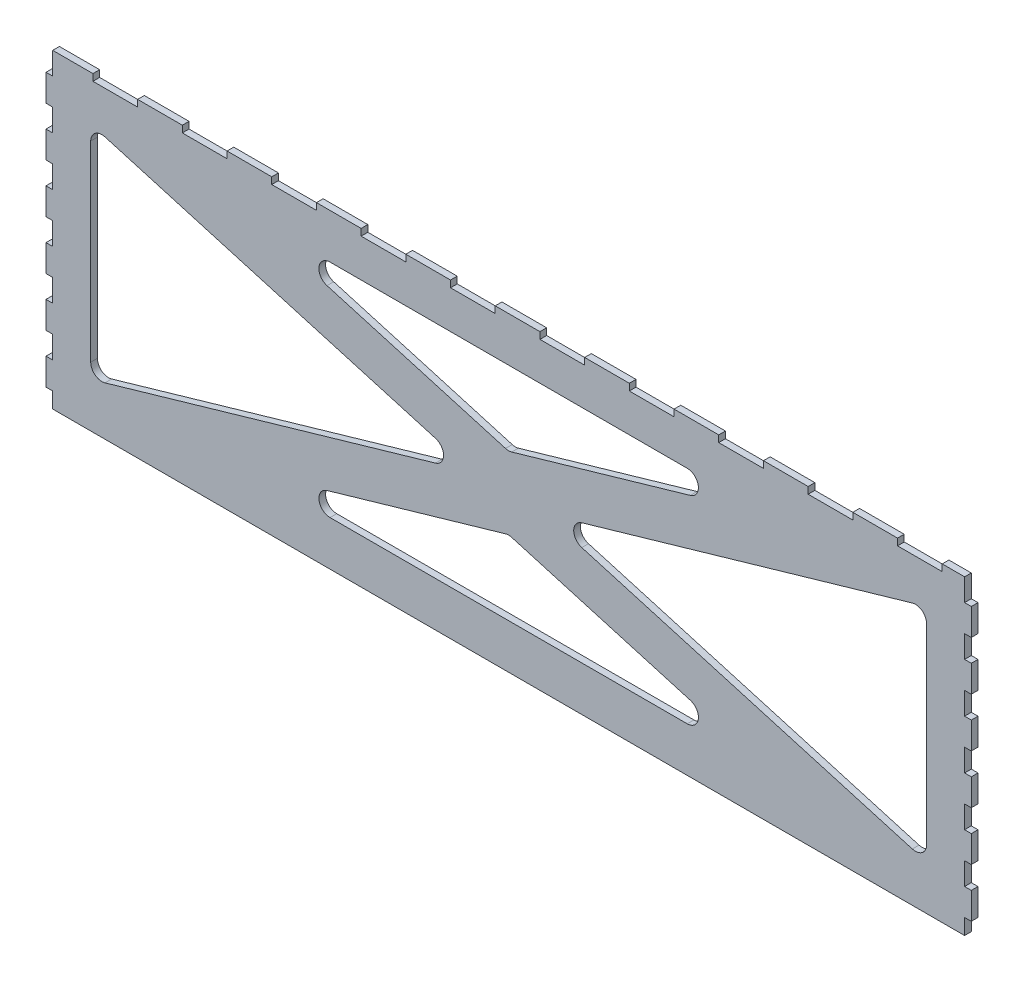
SolidWorks part; units mm, degrees
material "birch 3mm plywood"
ref_plane "Front Plane" through (0, 0, 0) normal (0, 0, 1) x (1, 0, 0)
ref_plane "Top Plane" through (0, 0, 0) normal (0, 1, 0) x (1, 0, 0)
ref_plane "Right Plane" through (0, 0, 0) normal (1, 0, 0) x (0, 0, -1)
sketch "Sketch1" plane through (0, 0, 152) normal (0, 0, 1) x (1, 0, 0)
  line L1 (-207, 69.5) -> (207, 69.5)
  line L2 (-207, 69.5) -> (-207, -69.5)
  line L3 (-207, -69.5) -> (207, -69.5)
  line L4 (207, 69.5) -> (207, -69.5)
  line L6 (-187, -42.8458) -> (-187, 42.8458)
  line L7 (-180.6086, 47.6483) -> (-32.7214, 4.8025)
  line L12 (200, -62.5) -> (-200, -62.5) construction
  line L13 (200, 62.5) -> (200, -62.5) construction
  line L14 (-200, -62.5) -> (-200, 62.5) construction
  line L15 (-200, 62.5) -> (200, 62.5) construction
  line L18 (79.903, 49.5) -> (-79.903, 49.5)
  line L19 (-32.7214, -4.8025) -> (-180.6086, -47.6483)
  line L20 (-81.2943, 39.6975) -> (-1.3914, 16.5481)
  line L21 (1.3914, 16.5481) -> (81.2943, 39.6975)
  line L23 (180.6086, 47.6483) -> (32.7214, 4.8025)
  line L24 (187, -42.8458) -> (187, 42.8458)
  line L25 (32.7214, -4.8025) -> (180.6086, -47.6483)
  line L26 (-200, 0) -> (200, 0) construction
  line L27 (-81.2943, -39.6975) -> (-1.3914, -16.5481)
  line L28 (79.903, -49.5) -> (-79.903, -49.5)
  line L29 (1.3914, -16.5481) -> (81.2943, -39.6975)
  line L30 (0, 16.145) -> (0, -16.145) construction
  line L31 (-16.145, 0) -> (16.145, 0) construction
  line L32 (0, 16.145) -> (0, -16.145) construction
  arc A0 (-180.6086, -47.6483) -> (-187, -42.8458) centre (-182, -42.8458) cw
  arc A1 (-32.7214, -4.8025) -> (-32.7214, 4.8025) centre (-34.1127, 0) ccw
  arc A2 (-180.6086, 47.6483) -> (-187, 42.8458) centre (-182, 42.8458) ccw
  arc A3 (81.2943, -39.6975) -> (79.903, -49.5) centre (79.903, -44.5) cw
  arc A4 (-81.2943, -39.6975) -> (-79.903, -49.5) centre (-79.903, -44.5) ccw
  arc A5 (-1.3914, -16.5481) -> (1.3914, -16.5481) centre (0, -21.3506) cw
  arc A6 (32.7214, 4.8025) -> (32.7214, -4.8025) centre (34.1127, 0) ccw
  arc A7 (180.6086, -47.6483) -> (187, -42.8458) centre (182, -42.8458) ccw
  arc A8 (187, 42.8458) -> (180.6086, 47.6483) centre (182, 42.8458) ccw
  arc A9 (-81.2943, 39.6975) -> (-79.903, 49.5) centre (-79.903, 44.5) cw
  arc A10 (81.2943, 39.6975) -> (79.903, 49.5) centre (79.903, 44.5) ccw
  arc A11 (1.3914, 16.5481) -> (-1.3914, 16.5481) centre (0, 21.3506) cw
  point P14 (0, 0)
  point P15 (0, 0)
  point P32 (-187, 49.5)
  point P35 (115.1288, -49.5)
  point P38 (-115.1288, -49.5)
  point P51 (-115.1288, 49.5)
  point P54 (115.1288, 49.5)
  dimension "D9" = 5
  dimension "D10" = 5
  dimension "D1" = 7
  dimension "D2" = 7
  dimension "D3" = 7
  dimension "D4" = 7
  dimension "D5" = 20
  dimension "D6" = 20
  dimension "D7" = 20
  dimension "D8" = 20
  dimension "D11" = 20
  dimension "D12" = 400
  dimension "D13" = 125
extrude "Boss-Extrude1" add sketch "Sketch1" along normal blind 3
sketch "Sketch2" plane through (-207, 0, 0) normal (-1, 0, 0) x (0, 0, 1)
  line L76 (152, -18.5) -> (152, -28.5)
  line L77 (152, -28.5) -> (155, -28.5)
  line L78 (155, -28.5) -> (155, -40.5)
  line L79 (155, -40.5) -> (152, -40.5)
  line L80 (152, -40.5) -> (152, -50.5)
  line L81 (152, -50.5) -> (155, -50.5)
  line L82 (155, -50.5) -> (155, -62.5)
  line L83 (155, -62.5) -> (152, -62.5)
  line L84 (152, -62.5) -> (152, -69.5)
  line L85 (152, -69.5) -> (316, -69.5)
  line L86 (316, -69.5) -> (316, -62.5)
  line L87 (316, -62.5) -> (313, -62.5)
  line L88 (313, -62.5) -> (313, -50.5)
  line L89 (313, -50.5) -> (316, -50.5)
  line L90 (316, -50.5) -> (316, -40.5)
  line L91 (316, -40.5) -> (313, -40.5)
  line L92 (313, -40.5) -> (313, -28.5)
  line L93 (313, -28.5) -> (316, -28.5)
  line L94 (316, -28.5) -> (316, -18.5)
  line L95 (316, -18.5) -> (313, -18.5)
  line L96 (313, -18.5) -> (313, -6.5)
  line L97 (313, -6.5) -> (316, -6.5)
  line L98 (316, -6.5) -> (316, 3.5)
  line L99 (316, 3.5) -> (313, 3.5)
  line L100 (313, 3.5) -> (313, 15.5)
  line L101 (313, 15.5) -> (316, 15.5)
  line L102 (316, 15.5) -> (316, 25.5)
  line L103 (316, 47.5) -> (313, 47.5)
  line L104 (313, 47.5) -> (313, 59.5)
  line L105 (313, 59.5) -> (316, 59.5)
  line L106 (316, 59.5) -> (316, 69.5)
  line L107 (316, 69.5) -> (305, 69.5)
  line L108 (305, 69.5) -> (305, 66.5)
  line L109 (305, 66.5) -> (295, 66.5)
  line L110 (295, 66.5) -> (295, 69.5)
  line L111 (295, 69.5) -> (283, 69.5)
  line L112 (283, 69.5) -> (283, 66.5)
  line L113 (283, 66.5) -> (273, 66.5)
  line L114 (273, 66.5) -> (273, 69.5)
  line L115 (273, 69.5) -> (261, 69.5)
  line L116 (261, 69.5) -> (261, 66.5)
  line L117 (261, 66.5) -> (251, 66.5)
  line L118 (251, 66.5) -> (251, 69.5)
  line L119 (251, 69.5) -> (239, 69.5)
  line L120 (239, 69.5) -> (239, 66.5)
  line L121 (239, 66.5) -> (229, 66.5)
  line L122 (229, 66.5) -> (229, 69.5)
  line L123 (229, 69.5) -> (217, 69.5)
  line L124 (217, 69.5) -> (217, 66.5)
  line L125 (217, 66.5) -> (207, 66.5)
  line L126 (207, 66.5) -> (207, 69.5)
  line L127 (207, 69.5) -> (195, 69.5)
  line L128 (195, 69.5) -> (195, 66.5)
  line L129 (195, 66.5) -> (185, 66.5)
  line L130 (185, 66.5) -> (185, 69.5)
  line L131 (185, 69.5) -> (173, 69.5)
  line L132 (173, 69.5) -> (173, 66.5)
  line L133 (173, 66.5) -> (163, 66.5)
  line L134 (163, 66.5) -> (163, 69.5)
  line L135 (163, 69.5) -> (152, 69.5)
  line L136 (152, 69.5) -> (152, 59.5)
  line L137 (152, 59.5) -> (155, 59.5)
  line L138 (155, 59.5) -> (155, 47.5)
  line L139 (155, 47.5) -> (152, 47.5)
  line L140 (152, 47.5) -> (152, 37.5)
  line L141 (152, 37.5) -> (155, 37.5)
  line L142 (155, 37.5) -> (155, 25.5)
  line L143 (155, 25.5) -> (152, 25.5)
  line L144 (152, 25.5) -> (152, 15.5)
  line L145 (152, 15.5) -> (155, 15.5)
  line L146 (155, 15.5) -> (155, 3.5)
  line L147 (155, 3.5) -> (152, 3.5)
  line L148 (152, 3.5) -> (152, -6.5)
  line L149 (152, -6.5) -> (155, -6.5)
  line L150 (155, -6.5) -> (155, -18.5)
  line L151 (155, -18.5) -> (152, -18.5)
  line L152 (152, -18.5) -> (152, -28.5)
  line L153 (152, -28.5) -> (155, -28.5)
  line L154 (155, -28.5) -> (155, -40.5)
  line L155 (155, -40.5) -> (152, -40.5)
  line L156 (152, -40.5) -> (152, -50.5)
  line L157 (152, -50.5) -> (155, -50.5)
  line L158 (155, -50.5) -> (155, -62.5)
  line L159 (155, -62.5) -> (152, -62.5)
  line L160 (152, -62.5) -> (152, -69.5)
  line L161 (152, -69.5) -> (316, -69.5)
  line L162 (316, -69.5) -> (316, -62.5)
  line L163 (316, -62.5) -> (313, -62.5)
  line L164 (313, -62.5) -> (313, -50.5)
  line L165 (313, -50.5) -> (316, -50.5)
  line L166 (316, -50.5) -> (316, -40.5)
  line L167 (316, -40.5) -> (313, -40.5)
  line L168 (313, -40.5) -> (313, -28.5)
  line L169 (313, -28.5) -> (316, -28.5)
  line L170 (316, -28.5) -> (316, -18.5)
  line L171 (316, -18.5) -> (313, -18.5)
  line L172 (313, -18.5) -> (313, -6.5)
  line L173 (313, -6.5) -> (316, -6.5)
  line L174 (316, -6.5) -> (316, 3.5)
  line L175 (316, 3.5) -> (313, 3.5)
  line L176 (313, 3.5) -> (313, 15.5)
  line L177 (313, 15.5) -> (316, 15.5)
  line L178 (316, 15.5) -> (316, 25.5)
  line L179 (316, 47.5) -> (313, 47.5)
  line L180 (313, 47.5) -> (313, 59.5)
  line L181 (313, 59.5) -> (316, 59.5)
  line L182 (316, 59.5) -> (316, 69.5)
  line L183 (316, 69.5) -> (305, 69.5)
  line L184 (305, 69.5) -> (305, 66.5)
  line L185 (305, 66.5) -> (295, 66.5)
  line L186 (295, 66.5) -> (295, 69.5)
  line L187 (295, 69.5) -> (283, 69.5)
  line L188 (283, 69.5) -> (283, 66.5)
  line L189 (283, 66.5) -> (273, 66.5)
  line L190 (273, 66.5) -> (273, 69.5)
  line L191 (273, 69.5) -> (261, 69.5)
  line L192 (261, 69.5) -> (261, 66.5)
  line L193 (261, 66.5) -> (251, 66.5)
  line L194 (251, 66.5) -> (251, 69.5)
  line L195 (251, 69.5) -> (239, 69.5)
  line L196 (239, 69.5) -> (239, 66.5)
  line L197 (239, 66.5) -> (229, 66.5)
  line L198 (229, 66.5) -> (229, 69.5)
  line L199 (229, 69.5) -> (217, 69.5)
  line L200 (217, 69.5) -> (217, 66.5)
  line L201 (217, 66.5) -> (207, 66.5)
  line L202 (207, 66.5) -> (207, 69.5)
  line L203 (207, 69.5) -> (195, 69.5)
  line L204 (195, 69.5) -> (195, 66.5)
  line L205 (195, 66.5) -> (185, 66.5)
  line L206 (185, 66.5) -> (185, 69.5)
  line L207 (185, 69.5) -> (173, 69.5)
  line L208 (173, 69.5) -> (173, 66.5)
  line L209 (173, 66.5) -> (163, 66.5)
  line L210 (163, 66.5) -> (163, 69.5)
  line L211 (163, 69.5) -> (152, 69.5)
  line L212 (152, 69.5) -> (152, 59.5)
  line L213 (152, 59.5) -> (155, 59.5)
  line L214 (155, 59.5) -> (155, 47.5)
  line L215 (155, 47.5) -> (152, 47.5)
  line L216 (152, 47.5) -> (152, 37.5)
  line L217 (152, 37.5) -> (155, 37.5)
  line L218 (155, 37.5) -> (155, 25.5)
  line L219 (155, 25.5) -> (152, 25.5)
  line L220 (152, 25.5) -> (152, 15.5)
  line L221 (152, 15.5) -> (155, 15.5)
  line L222 (155, 15.5) -> (155, 3.5)
  line L223 (155, 3.5) -> (152, 3.5)
  line L224 (152, 3.5) -> (152, -6.5)
  line L225 (152, -6.5) -> (155, -6.5)
  line L226 (155, -6.5) -> (155, -18.5)
  line L227 (155, -18.5) -> (152, -18.5)
  line L692 (316, 25.5) -> (313, 25.5)
  line L693 (316, 25.5) -> (313, 25.5)
  line L694 (313, 25.5) -> (313, 37.5)
  line L695 (313, 25.5) -> (313, 37.5)
  line L696 (313, 37.5) -> (316, 37.5)
  line L697 (313, 37.5) -> (316, 37.5)
  line L698 (316, 37.5) -> (316, 47.5)
  line L699 (316, 37.5) -> (316, 47.5)
  dimension "D1" = 0
extrude "Cut-Extrude1" cut sketch "Sketch2" against normal blind 3 contours L199 L200 L201 L202 L203 L204 L205 L206 L207 L208 L209 L210 L211 L212 L213 L214 L215 L216 L217 L218 L219 L220 L221 L222 L223 L224 L225 L226 L227 L152 L153 L154 L155 L156 L157 L158 L159 L160 L161 L162 L163 L164 L165 L166 L167 L168 L169 L170 L171 L172 L173 L174 L175 L176 L177 L178 L693 L695 L697 L699 L179 L180 L181 L182 L183 L184 L185 L186 L187 L188 L189 L190 L191 L192 L193 L194 L195 L196 L197 L198
mirror "Mirror1" about plane through (0, 0, 0) normal (1, 0, 0) of "Cut-Extrude1"
sketch "Sketch3" plane through (0, 0, 152) normal (0, 0, -1) x (-1, 0, 0)
  line L0 (-204, 69.5) -> (204, 69.5) construction
  line L1 (-194, 69.5) -> (-174, 69.5)
  line L2 (-194, 69.5) -> (-194, 66.5)
  line L3 (-194, 66.5) -> (-174, 66.5)
  line L4 (-174, 69.5) -> (-174, 66.5)
  line L5 (-154, 69.5) -> (-154, 66.5)
  line L6 (-154, 69.5) -> (-134, 69.5)
  line L7 (-134, 69.5) -> (-134, 66.5)
  line L8 (-154, 66.5) -> (-134, 66.5)
  line L9 (-114, 69.5) -> (-114, 66.5)
  line L10 (-114, 69.5) -> (-94, 69.5)
  line L11 (-94, 69.5) -> (-94, 66.5)
  line L12 (-114, 66.5) -> (-94, 66.5)
  line L13 (-74, 69.5) -> (-74, 66.5)
  line L14 (-74, 69.5) -> (-54, 69.5)
  line L15 (-54, 69.5) -> (-54, 66.5)
  line L16 (-74, 66.5) -> (-54, 66.5)
  line L17 (-34, 69.5) -> (-34, 66.5)
  line L18 (-34, 69.5) -> (-14, 69.5)
  line L19 (-14, 69.5) -> (-14, 66.5)
  line L20 (-34, 66.5) -> (-14, 66.5)
  line L21 (6, 69.5) -> (6, 66.5)
  line L22 (6, 69.5) -> (26, 69.5)
  line L23 (26, 69.5) -> (26, 66.5)
  line L24 (6, 66.5) -> (26, 66.5)
  line L25 (46, 69.5) -> (46, 66.5)
  line L26 (46, 69.5) -> (66, 69.5)
  line L27 (66, 69.5) -> (66, 66.5)
  line L28 (46, 66.5) -> (66, 66.5)
  line L29 (86, 69.5) -> (86, 66.5)
  line L30 (86, 69.5) -> (106, 69.5)
  line L31 (106, 69.5) -> (106, 66.5)
  line L32 (86, 66.5) -> (106, 66.5)
  line L33 (126, 69.5) -> (126, 66.5)
  line L34 (126, 69.5) -> (146, 69.5)
  line L35 (146, 69.5) -> (146, 66.5)
  line L36 (126, 66.5) -> (146, 66.5)
  line L37 (166, 69.5) -> (166, 66.5)
  line L38 (166, 69.5) -> (186, 69.5)
  line L39 (186, 69.5) -> (186, 66.5)
  line L40 (166, 66.5) -> (186, 66.5)
  dimension "D1" = 3
  dimension "D2" = 20
  dimension "D3" = 10
  dimension "D5" = 20
  dimension "D4" = 10
extrude "Cut-Extrude2" cut sketch "Sketch3" against normal blind 3
